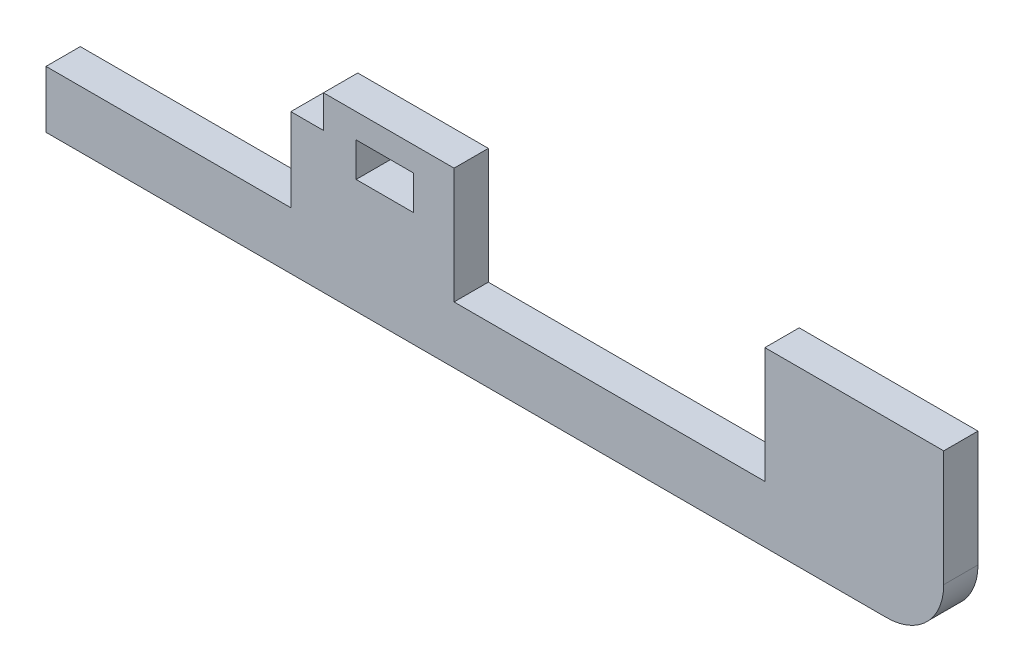
SolidWorks part; units mm, degrees
ref_plane "Front Plane" through (0, 0, 0) normal (0, 0, 1) x (1, 0, 0)
ref_plane "Top Plane" through (0, 0, 0) normal (0, 1, 0) x (1, 0, 0)
ref_plane "Right Plane" through (0, 0, 0) normal (1, 0, 0) x (0, 0, -1)
sketch "Sketch1" plane through (0, 0, 0) normal (0, 0, 1) x (1, 0, 0)
  line L1 (-37.7297, 18.8387) -> (101.9703, 18.8387)
  line L2 (-37.7297, 18.8387) -> (-37.7297, -8.0853)
  line L3 (-37.7297, -8.0853) -> (101.9703, -8.0853)
  line L4 (101.9703, 18.8387) -> (101.9703, -8.0853)
  dimension "D1" = 26.924
  dimension "D2" = 139.7
extrude "Boss-Extrude1" add sketch "Sketch1" along normal blind 5.334
sketch "Sketch2" plane through (0, 0, 5.334) normal (0, 0, 1) x (1, 0, 0)
  line L0 (-37.7297, -8.0853) -> (101.9703, -8.0853) construction
  line L1 (-37.7297, 18.8387) -> (0.3703, 18.8387)
  line L2 (-37.7297, 18.8387) -> (-37.7297, 0.8047)
  line L3 (-37.7297, 0.8047) -> (0.3703, 0.8047)
  line L4 (0.3703, 18.8387) -> (0.3703, 0.8047)
  dimension "D1" = 38.1
  dimension "D2" = 8.89
extrude "Cut-Extrude1" cut sketch "Sketch2" against normal through all
sketch "Sketch3" plane through (0, 0, 5.334) normal (0, 0, 1) x (1, 0, 0)
  line L0 (101.9703, 18.8387) -> (0.3703, 18.8387) construction
  line L1 (25.7703, 18.8387) -> (74.1421, 18.8387)
  line L2 (25.7703, 18.8387) -> (25.7703, 0.8047)
  line L3 (25.7703, 0.8047) -> (74.1421, 0.8047)
  line L4 (74.1421, 18.8387) -> (74.1421, 0.8047)
  line L5 (0.3703, 0.8047) -> (0.3703, 18.8387) construction
  line L6 (-37.7297, 0.8047) -> (0.3703, 0.8047) construction
  dimension "D1" = 25.4
  dimension "D2" = 48.3718
  dimension "D3" = 0
extrude "Cut-Extrude3" cut sketch "Sketch3" against normal through all
sketch "Sketch4" plane through (0, 0, 5.334) normal (0, 0, 1) x (1, 0, 0)
  line L1 (0.3703, 18.8387) -> (5.4503, 18.8387)
  line L2 (0.3703, 18.8387) -> (0.3703, 13.7587)
  line L3 (0.3703, 13.7587) -> (5.4503, 13.7587)
  line L4 (5.4503, 18.8387) -> (5.4503, 13.7587)
  dimension "D1" = 5.08
  dimension "D2" = 5.08
extrude "Cut-Extrude4" cut sketch "Sketch4" against normal through all
fillet "Fillet1" radius 8.89 1 edges at (101.9703, -8.0853, 2.667)
sketch "Sketch5" plane through (0, 0, 5.334) normal (0, 0, 1) x (1, 0, 0)
  line L0 (0.3703, 9.6947) -> (25.7703, 9.6947) construction
  line L1 (19.4203, 9.6947) -> (10.5303, 9.6947)
  line L2 (19.4203, 9.6947) -> (19.4203, 15.0287)
  line L3 (19.4203, 15.0287) -> (10.5303, 15.0287)
  line L4 (10.5303, 9.6947) -> (10.5303, 15.0287)
  line L5 (25.7703, 18.8387) -> (25.7703, 0.8047) construction
  dimension "D1" = 5.334
  dimension "D2" = 8.89
  dimension "D3" = 6.35
extrude "Cut-Extrude5" cut sketch "Sketch5" against normal through all
equation "\"MDF\"= .21in"
equation "\"Foamcore\"= .13in"
equation "\"Gmaterial\"= \"MDF\""
equation "\"D1@Boss-Extrude1\"=\"MDF\""
equation "\"D1@Sketch5\"=\"MDF\""
